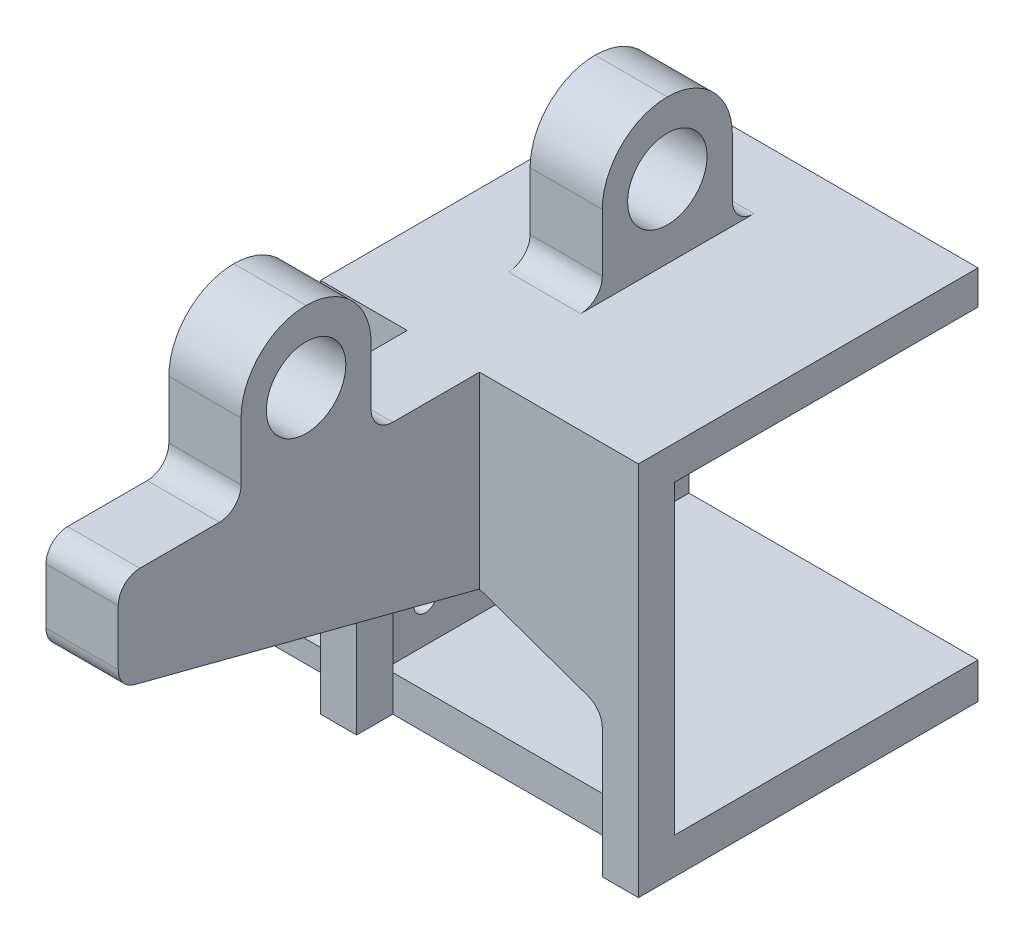
SolidWorks part; units mm, degrees
ref_plane "Front Plane" through (0, 0, 0) normal (0, 0, 1) x (1, 0, 0)
ref_plane "Top Plane" through (0, 0, 0) normal (0, 1, 0) x (1, 0, 0)
ref_plane "Right Plane" through (0, 0, 0) normal (1, 0, 0) x (0, 0, -1)
sketch "Sketch1" plane through (0, 0, 0) normal (0, 1, 0) x (1, 0, 0)
  line L1 (0, 0) -> (94, 0)
  line L2 (0, 0) -> (0, -42)
  line L3 (0, -42) -> (94, -42)
  line L4 (94, 0) -> (94, -42)
  dimension "D1" = 94
  dimension "D2" = 42
extrude "Boss-Extrude1" add sketch "Sketch1" along normal blind 3
sketch "Sketch2" plane through (0, 0, 0) normal (0, -1, 0) x (1, 0, 0)
  line L0 (94, 0) -> (0, 0) construction
  line L1 (0, 42) -> (4, 42)
  line L2 (0, 42) -> (0, 0)
  line L3 (0, 0) -> (4, 0)
  line L4 (4, 42) -> (4, 0)
  line L6 (94, 42) -> (90, 42)
  line L7 (94, 42) -> (94, 0)
  line L8 (94, 0) -> (90, 0)
  line L9 (90, 42) -> (90, 0)
  dimension "D1" = 4
  dimension "D2" = 4
extrude "Boss-Extrude2" add sketch "Sketch2" against normal blind 47
sketch "Sketch3" plane through (94, 0, 0) normal (1, 0, 0) x (0, 0, -1)
  circle B0 centre (-21, 26) radius 12.5
  circle B1 centre (-36.5, 41.5) radius 1.6
  circle B2 centre (-5.5, 41.5) radius 1.6
  circle B3 centre (-36.5, 10.5) radius 1.6
  circle B4 centre (-5.5, 10.5) radius 1.6
sketch_block_instance "stepper mounting hole pattern-1"
sketch_block "stepper mounting hole pattern" parameters "D1"=25, "D2"=3.2, "D3"=3.2, "D4"=3.2, "D5"=3.2
extrude "Cut-Extrude1" cut sketch "Sketch3" against normal through all
sketch "Sketch4" plane through (94, 0, 0) normal (1, 0, 0) x (0, 0, -1)
  line L0 (0, 47) -> (0, 0) construction
  line L1 (-42, 0) -> (0, 0)
  line L2 (-42, 0) -> (-42, 5)
  line L3 (-42, 5) -> (0, 5)
  line L4 (0, 0) -> (0, 5)
  dimension "D1" = 5
extrude "Boss-Extrude3" add sketch "Sketch4" along normal blind 40
sketch "Sketch5" plane through (0, 0, 0) normal (-1, 0, 0) x (0, 0, 1)
  line L0 (42, 47) -> (42, 0) construction
  line L1 (0, 0) -> (42, 0)
  line L2 (0, 0) -> (0, 5)
  line L3 (0, 5) -> (42, 5)
  line L4 (42, 0) -> (42, 5)
  dimension "D1" = 5
extrude "Boss-Extrude4" add sketch "Sketch5" along normal blind 38
sketch "Sketch7" plane through (0, 47, 0) normal (0, 1, 0) x (1, 0, 0)
  line L0 (-38, -42) -> (0, -42) construction
  line L1 (4, 0) -> (-38, 0)
  line L2 (4, 0) -> (4, -42)
  line L3 (4, -42) -> (-38, -42)
  line L4 (-38, 0) -> (-38, -42)
  line L5 (134, -42) -> (94, -42) construction
  line L6 (90, 0) -> (134, 0)
  line L7 (90, 0) -> (90, -42)
  line L8 (90, -42) -> (134, -42)
  line L9 (134, 0) -> (134, -42)
extrude "Boss-Extrude6" add sketch "Sketch7" along normal blind 5
sketch "Sketch9" plane through (0, 3, 0) normal (0, 1, 0) x (1, 0, 0)
  line L0 (4, -42) -> (90, -42) construction
  line L1 (90, 0) -> (90, -42) construction
  line L2 (90, 0) -> (4, 0) construction
  line L4 (4, -42) -> (4, 0) construction
  circle A0 centre (83, -21) radius 2.15
  circle A1 centre (65, -21) radius 2.15
  circle A2 centre (74, -12) radius 2.15
  circle A3 centre (74, -30) radius 2.15
  circle A4 centre (22, -12) radius 2.15
  circle A5 centre (22, -30) radius 2.15
  dimension "D1" = 4.3
  dimension "D2" = 21
  dimension "D3" = 7
  dimension "D4" = 18
  dimension "D5" = 9
  dimension "D6" = 18
  dimension "D7" = 9
  dimension "D8" = 18
  dimension "D9" = 12
  dimension "D10" = 18
extrude "Cut-Extrude2" cut sketch "Sketch9" against normal through all
sketch "Sketch11" plane through (0, 52, 0) normal (0, 1, 0) x (1, 0, 0)
  line L0 (4, -42) -> (4, 0) construction
  line L1 (-13, -12) -> (-3, -12)
  line L2 (-13, -12) -> (-13, -30)
  line L3 (-13, -30) -> (-3, -30)
  line L4 (-3, -12) -> (-3, -30)
  line L5 (4, 0) -> (-38, 0) construction
  line L7 (102, -12) -> (112, -12)
  line L8 (102, -12) -> (102, -30)
  line L9 (102, -30) -> (112, -30)
  line L10 (112, -12) -> (112, -30)
  line L11 (90, 0) -> (90, -42) construction
  dimension "D1" = 10
  dimension "D2" = 7
  dimension "D3" = 18
  dimension "D4" = 12
  dimension "D5" = 18
  dimension "D6" = 10
  dimension "D7" = 12
extrude "Boss-Extrude7" add sketch "Sketch11" along normal blind 20
sketch "Sketch13" plane through (-13, 0, 0) normal (-1, 0, 0) x (0, 0, 1)
  line L0 (0, 0) -> (42, 0) construction
  line L1 (12, 72) -> (12, 52) construction
  circle A0 centre (21, 62.15) radius 5.5
  dimension "D2" = 11
  dimension "D1" = 62.15
  dimension "D3" = 9
extrude "Cut-Extrude3" cut sketch "Sketch13" against normal through all
sketch "Sketch20" plane through (0, 0, 42) normal (0, 0, 1) x (1, 0, 0)
  line L0 (134, 0) -> (134, 52)
  line L1 (134, 52) -> (90, 52)
  line L2 (90, 52) -> (90, 0)
  line L3 (-38, 0) -> (134, 0) construction
  line L4 (90, 0) -> (95, 0)
  line L5 (95, 0) -> (95, 20)
  line L6 (95, 20) -> (102, 26)
  line L7 (102, 26) -> (112, 26)
  line L8 (112, 26) -> (129, 20)
  line L9 (129, 20) -> (129, 0)
  line L10 (129, 0) -> (134, 0)
  dimension "D1" = 5
  dimension "D2" = 5
  dimension "D3" = 10
  dimension "D4" = 7
  dimension "D5" = 20
  dimension "D6" = 6
extrude "Boss-Extrude11" add sketch "Sketch20" along normal blind 5
sketch "Sketch23" plane through (0, 0, 47) normal (0, 0, 1) x (1, 0, 0)
  line L0 (134, 52) -> (90, 52) construction
  line L1 (102, 52) -> (112, 52)
  line L2 (102, 52) -> (102, 26)
  line L3 (102, 26) -> (112, 26)
  line L4 (112, 52) -> (112, 26)
  line L5 (102, 52) -> (112, 52) construction
extrude "Boss-Extrude12" add sketch "Sketch23" along normal blind 50
sketch "Sketch24" plane through (112, 0, 0) normal (1, 0, 0) x (0, 0, -1)
  line L0 (-47, 26) -> (-97, 39)
  line L1 (-97, 26) -> (-97, 52) construction
  line L2 (-97, 39) -> (-97, 26)
  line L3 (-97, 26) -> (-47, 26)
extrude "Cut-Extrude7" cut sketch "Sketch24" against normal through all
sketch "Sketch25" plane through (0, 52, 0) normal (0, 1, 0) x (1, 0, 0)
  line L0 (102, -97) -> (102, -47) construction
  line L1 (102, -62) -> (112, -62)
  line L2 (102, -62) -> (102, -80)
  line L3 (102, -80) -> (112, -80)
  line L4 (112, -62) -> (112, -80)
  line L5 (112, -97) -> (112, -47) construction
  line L6 (102, -30) -> (112, -30) construction
  dimension "D1" = 18
  dimension "D2" = 32
extrude "Boss-Extrude13" add sketch "Sketch25" along normal blind 20
sketch "Sketch26" plane through (112, 0, 0) normal (1, 0, 0) x (0, 0, -1)
  line L0 (-80, 72) -> (-80, 52) construction
  line L1 (-47, 0) -> (0, 0) construction
  circle A0 centre (-71, 62.15) radius 5.5
  dimension "D1" = 11
  dimension "D2" = 9
  dimension "D3" = 62.15
extrude "Cut-Extrude8" cut sketch "Sketch26" against normal through all
sketch "Sketch27" plane through (0, 3, 0) normal (0, 1, 0) x (1, 0, 0)
  line L0 (90, 0) -> (90, -42) construction
  line L1 (41, -12) -> (53, -12)
  line L2 (41, -12) -> (41, -30)
  line L3 (41, -30) -> (53, -30)
  line L4 (53, -12) -> (53, -30)
  line L5 (4, -42) -> (90, -42) construction
  dimension "D1" = 37
  dimension "D2" = 18
  dimension "D3" = 12
  dimension "D4" = 12
extrude "Boss-Extrude14" add sketch "Sketch27" along normal blind 69
sketch "Sketch28" plane through (53, 0, 0) normal (1, 0, 0) x (0, 0, -1)
  line L0 (-12, 72) -> (-12, 3) construction
  line L1 (-47, 0) -> (0, 0) construction
  circle A0 centre (-21, 62.15) radius 5.5
  dimension "D1" = 11
  dimension "D2" = 9
  dimension "D3" = 62.15
extrude "Cut-Extrude10" cut sketch "Sketch28" against normal blind 5
sketch "Sketch29" plane through (41, 0, 0) normal (-1, 0, 0) x (0, 0, 1)
  line L0 (30, 72) -> (30, 3) construction
  line L2 (0, 0) -> (42, 0) construction
  circle A0 centre (21, 62.15) radius 5.5
  dimension "D2" = 11
  dimension "D1" = 9
  dimension "D3" = 62.15
extrude "Cut-Extrude11" cut sketch "Sketch29" against normal blind 5
fillet "Fillet4" radius 9 8 edges at (-8, 72, 12) (-8, 72, 30) (107, 72, 12) (107, 72, 30) (107, 72, 62) (107, 72, 80) (47, 72, 12) (47, 72, 30)
fillet "Fillet3" radius 3 14 edges at (-8, 52, 12) (-8, 52, 30) (107, 52, 12) (107, 52, 30) (107, 52, 62) (107, 52, 80) (129, 20, 44.5) (112, 26, 44.5) (102, 26, 44.5) (95, 20, 44.5) (107, 52, 97) (107, 39, 97) (47, 3, 12) (47, 3, 30)
sketch "Sketch30" plane through (0, 0, 0) normal (0, -1, 0) x (1, 0, 0)
  line L0 (-38, 42) -> (90, 42) construction
  line L1 (53, 42) -> (-38, 42)
  line L2 (53, 42) -> (53, 0)
  line L3 (53, 0) -> (-38, 0)
  line L4 (-38, 42) -> (-38, 0)
extrude "Cut-Extrude12" cut sketch "Sketch30" against normal through all
sketch "Sketch31" plane through (0, 0, 0) normal (0, 0, -1) x (-1, 0, 0)
  line L1 (-134, 47) -> (-94, 47)
  line L2 (-134, 47) -> (-134, 47.3)
  line L3 (-134, 47.3) -> (-94, 47.3)
  line L4 (-94, 47) -> (-94, 47.3)
  dimension "D1" = 0.3
  dimension "D2" = 40
extrude "Cut-Extrude13" cut sketch "Sketch31" against normal blind 42
